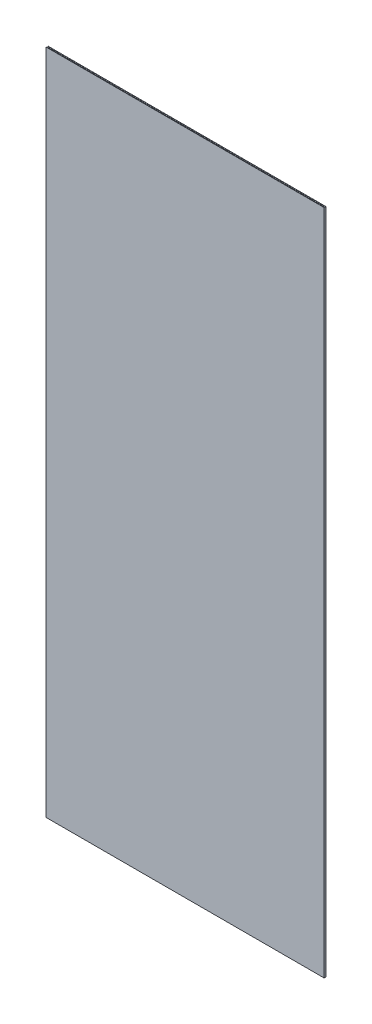
SolidWorks part; units mm, degrees
ref_plane "Front Plane" through (0, 0, 0) normal (0, 0, 1) x (1, 0, 0)
ref_plane "Top Plane" through (0, 0, 0) normal (0, 1, 0) x (1, 0, 0)
ref_plane "Right Plane" through (0, 0, 0) normal (1, 0, 0) x (0, 0, -1)
sketch "Sketch1" plane through (0, 0, 0) normal (0, 1, 0) x (1, 0, 0)
  line L0 (5, -4) -> (-5.3, -4)
  line L1 (-5.3, -4) -> (5, -4) construction
  line L2 (-5, -4) -> (-5, 4) construction
  line L3 (-5.3, 4) -> (5, 4) construction
  line L4 (5, -4) -> (5, 4) construction
  line L5 (-5, -4) -> (5, 4) construction
  line L6 (-5, 4) -> (5, -4) construction
  line L7 (4.7, -3.7) -> (4.7, 3.7)
  line L8 (-5.3, 3.7) -> (4.7, 3.7)
  line L9 (-5.3, -3.7) -> (4.7, -3.7)
  line L10 (5, 4) -> (5, -4)
  line L11 (-5, 4) -> (5, 4) construction
  line L12 (-5, 3.7) -> (5, 3.7) construction
  line L13 (-5, -3.7) -> (5, -3.7) construction
  line L14 (-5, -4) -> (5, -4) construction
  line L15 (5, 4) -> (-5.3, 4)
  line L16 (-5.3, 4) -> (-5.3, -4) construction
  line L17 (-5.3, 4) -> (-5.3, 3.7)
  line L18 (4.7, -4) -> (4.7, 4) construction
  line L19 (-5.3, -3.7) -> (-5.3, -4)
  point P0 (0, 0)
  dimension "D1" = 8
  dimension "D2" = 10
  dimension "D6" = 0.3
  dimension "D3" = 0.3
  dimension "D4" = 0.3
  dimension "D5" = 0.3
extrude "Boss-Extrude1" add sketch "Sketch1" along normal blind 3000
pattern_linear "LPattern1" count 125 spacing 10 along (1, 0, 0) of "Boss-Extrude1"
